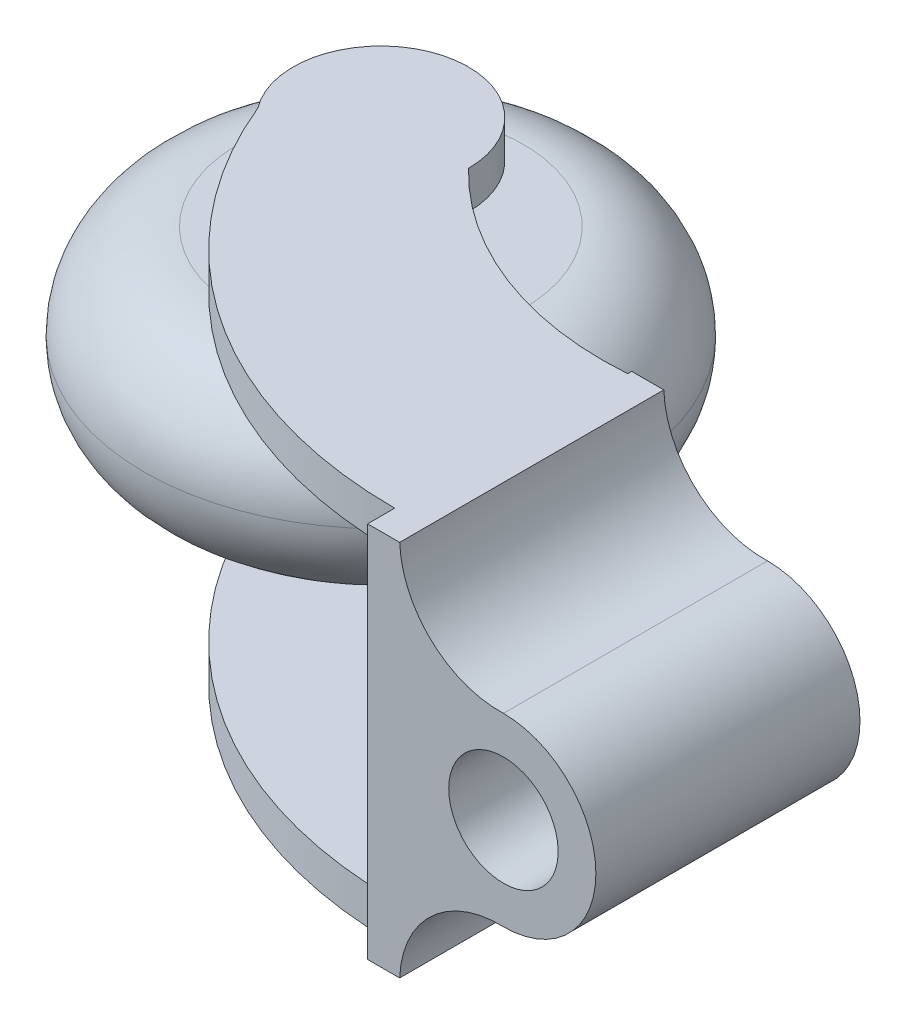
SolidWorks part; units mm, degrees
material "Brass"
ref_plane "Front Plane" through (0, 0, 0) normal (0, 0, 1) x (1, 0, 0)
ref_plane "Top Plane" through (0, 0, 0) normal (0, 1, 0) x (1, 0, 0)
ref_plane "Right Plane" through (0, 0, 0) normal (1, 0, 0) x (0, 0, -1)
sketch "Sketch1" plane through (0, 0, 0) normal (0, 1, 0) x (1, 0, 0)
  circle A0 centre (0, 0) radius 12.55
  circle A1 centre (0, 0) radius 1.925
  dimension "D1" = 3.85
  dimension "D2" = 25.1
extrude "Boss-Extrude1" add sketch "Sketch1" along normal blind 10
fillet "Fillet1" radius 5 2 edges at (0, 0, 12.55) (0, 10, 12.55)
sketch "Sketch2" plane through (0, 0, 0) normal (0, -1, 0) x (1, 0, 0)
  circle A0 centre (0, 0) radius 1.925
  dimension "D1" = 3.85
extrude "Boss-Extrude2" add sketch "Sketch2" along normal blind 5 and the other way blind 15
sketch "Sketch3" plane through (0, -5, 0) normal (0, -1, 0) x (1, 0, 0)
  line L0 (20, 17.5) -> (20, 5)
  circle A0 centre (0, 0) radius 4.65
  arc A1 (4.65, 0) -> (20, 5) centre (17.0198, -11.9131) cw
  arc A2 (-4.65, 0) -> (20, 17.5) centre (18.2711, -6.1754) cw
  circle M2 centre (0, 0) radius 1.925
  dimension "D1" = 9.3
  dimension "D2" = 12.5
  dimension "D3" = 20
  dimension "D4" = 5
extrude "Boss-Extrude3" add sketch "Sketch3" against normal blind 2 contours A2 A0 A1 L0 | A2 A0 M2 | A0 region at (10.3495, -5, 9.5679) region at (1.4468, -5, 4.2806)
extrude "Boss-Extrude4" add sketch "Sketch3<3>" along normal blind 2 from surface contours A2 A0 M2 | A2 A0 A1 L0 | A0 region at (10.3495, -5, 9.5679) region at (1.4468, -5, 4.2806) starting at face at (0, 15, -1.925)
sketch "Sketch3<3>" plane through (0, -5, 0) normal (0, -1, 0) x (1, 0, 0) same geometry as "Sketch3"
sketch "Sketch4" plane through (20, 0, 0) normal (1, 0, 0) x (0, 0, -1)
  line L1 (-17.5, -5) -> (-5, -5)
  line L2 (-17.5, -5) -> (-17.5, 15)
  line L3 (-17.5, 15) -> (-5, 15)
  line L4 (-5, -5) -> (-5, 15)
  line L5 (-17.5, -5) -> (-5, 15) construction
  line L6 (-17.5, 15) -> (-5, -5) construction
  point P4 (-11.25, 5)
extrude "Boss-Extrude5" add sketch "Sketch4" against normal blind 1.7
sketch "Sketch5" plane through (0, 0, 5) normal (0, 0, -1) x (-1, 0, 0)
  line L0 (-18.3, 5) -> (-35.8766, 5) construction
  line L1 (-18.3, -5) -> (-18.3, 15) construction
  line L2 (-20, 15) -> (-20, -5) construction
  line L3 (-20, -5) -> (-18.3, -5)
  line L4 (-18.3, -5) -> (-18.3, 15)
  line L5 (-18.3, 15) -> (-20, 15)
  circle A0 centre (-25.5, 5) radius 4.9
  circle A1 centre (-25.5, 5) radius 2.9
  arc A2 (-20, -5) -> (-25.5, 0.1) centre (-25.3, -5.2) ccw
  arc A3 (-20, 15) -> (-25.5, 9.9) centre (-25.3, 15.2) cw
  line M2 (-20, 15) -> (-20, -5)
  line M3 (-20, -5) -> (-18.3, -5)
  line M4 (-18.3, -5) -> (-18.3, 15)
  line M5 (-18.3, 15) -> (-20, 15)
  dimension "D1" = 9.8
  dimension "D2" = 2
  dimension "D3" = 5.5
extrude "Boss-Extrude6" add sketch "Sketch5" against normal blind 14 contours L0 A3 A0 M2 | L0 A0 A2 M2 | A0 L0 A1 A2 | L0 A0 A3 A1 | L0 M4 M2 M3 | L0 L4 M5 M2 region at (22.0469, 1.6797, 5) region at (21.1844, 9.4909, 5) region at (21.6, 5.1096, 5) region at (21.1844, 0.5091, 5) region at (19.15, 10, 5) region at (19.15, 0, 5)
